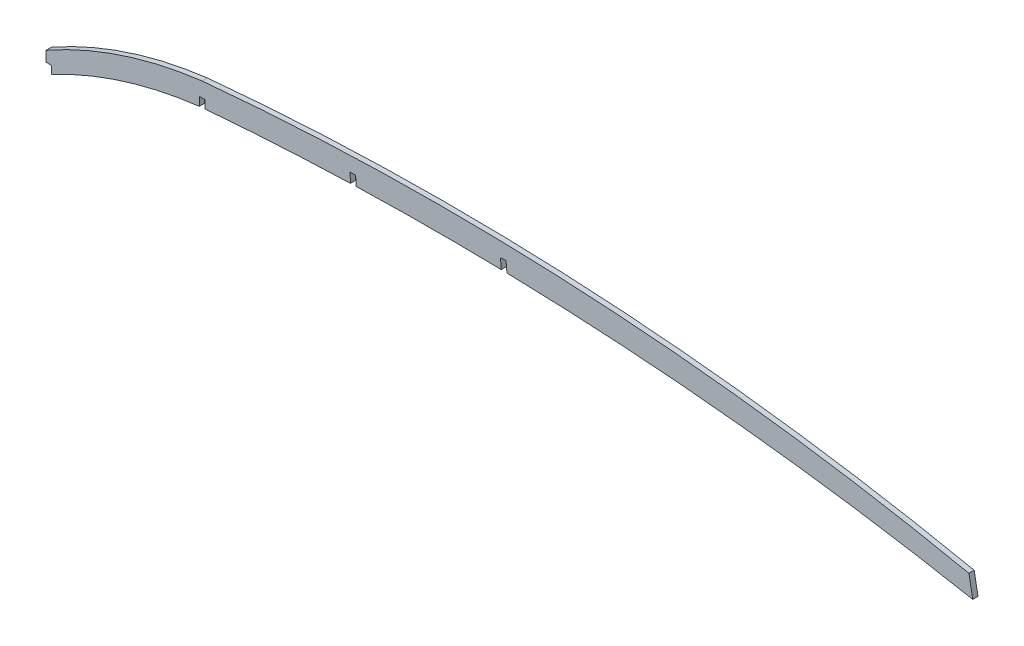
SolidWorks part; units mm, degrees
material "Balsa"
ref_plane "Front Plane" through (0, 0, 0) normal (0, 0, 1) x (1, 0, 0)
ref_plane "Top Plane" through (0, 0, 0) normal (0, 1, 0) x (1, 0, 0)
ref_plane "Right Plane" through (0, 0, 0) normal (1, 0, 0) x (0, 0, -1)
sketch "Sketch1" plane through (0, 0, 0) normal (0, 0, 1) x (1, 0, 0)
  line L2 (0, 0) -> (0, 169.3685) construction
  line L4 (93.98, 106.68) -> (556.5761, 106.68) construction
  line L9 (0, 106.68) -> (93.98, 106.68) construction
  line L14 (555.6382, 111.8229) -> (555.6382, 106.68) construction
  line L17 (555.6382, 111.8229) -> (557.917, 99.3265)
  line L19 (0, 106.68) -> (0, 93.98)
  line L20 (93.98, 137.668) -> (93.98, 123.7947) construction
  arc A6 (0, 106.68) -> (93.98, 137.668) centre (125.0054, -114.43) cw
  arc A8 (93.98, 137.668) -> (555.6382, 111.8229) centre (239.5165, -1398.7972) cw
  arc A9 (0, 93.98) -> (93.98, 123.7947) centre (122.3372, -128.6174) cw
  arc A25 (93.98, 123.7947) -> (557.917, 99.3265) centre (236.8486, -1577.8511) cw
  dimension "D4" = 254
  dimension "D2" = 93.98
  dimension "D8" = 1543.3426
  dimension "D9" = 100.334
  dimension "D3" = 30.988
  dimension "D12" = 254
  dimension "D14" = 1707.6328
  dimension "D1" = 106.68
  dimension "D5" = 462.5961
  dimension "D6" = 0.9378
  dimension "D7" = 5.1429
  dimension "D10" = 12.7025
  dimension "D11" = 12.7
  dimension "D13" = 13.8733
extrude "Boss-Extrude1" add sketch "Sketch1" along normal blind 3.175 contours A9 A25 L17 A8 A6 L19 region at (551.2665, 104.5698, 0)
sketch "Sketch2" plane through (0, 0, 3.175) normal (0, 0, 1) x (1, 0, 0)
  line L0 (0, 0) -> (0, 93.98) construction
  line L1 (0, 0) -> (93.98, 0) construction
  line L2 (93.98, 0) -> (93.98, 128.7725) construction
  line L3 (93.98, 0) -> (190.373, 0) construction
  line L4 (0, 93.98) -> (3.3528, 93.98)
  line L5 (0, 93.98) -> (0, 100.457)
  line L6 (0, 100.457) -> (3.3528, 100.457)
  line L7 (3.3528, 93.98) -> (3.3528, 100.457)
  line L8 (92.2909, 128.8487) -> (95.6691, 128.8487)
  line L9 (92.2909, 128.8487) -> (92.2909, 116.1487)
  line L10 (92.2909, 116.1487) -> (95.6691, 116.1487)
  line L11 (95.6691, 128.8487) -> (95.6691, 116.1487)
  line L12 (190.373, 0) -> (184.7454, 134.6815) construction
  line L15 (183.0546, 134.6871) -> (186.4298, 134.8282)
  line L16 (183.0546, 134.6871) -> (183.5848, 121.9982)
  line L17 (186.4298, 134.8282) -> (186.96, 122.1393)
  line L18 (183.5848, 121.9982) -> (186.96, 122.1393)
  line L21 (184.7454, 134.6815) -> (182.7802, 134.5994) construction
  line L22 (295.918, -122.9242) -> (299.0813, -122.6519)
  line L23 (276.8619, 135.4735) -> (273.6986, 135.2013)
  line L24 (298.5332, -116.2845) -> (295.3699, -116.5568)
  line L25 (274.2467, 128.8339) -> (277.41, 129.1062)
  line L26 (273.6986, 135.2013) -> (274.2467, 128.8339)
  line L27 (295.3699, -116.5568) -> (295.918, -122.9242)
  line L28 (276.8619, 135.4735) -> (277.41, 129.1062)
  line L29 (298.5332, -116.2845) -> (299.0813, -122.6519)
  line L30 (298.5332, -116.2845) -> (299.0813, -122.6519)
  line L32 (295.3699, -116.5568) -> (295.918, -122.9242)
  line L35 (298.5332, -116.2845) -> (295.3699, -116.5568)
  line L37 (295.918, -122.9242) -> (299.0813, -122.6519)
  line L38 (190.373, 0) -> (508.8709, 0) construction
  line L39 (275.2802, 135.3374) -> (286.9301, 0) construction
  line L41 (273.5908, 135.2685) -> (276.9566, 135.5582)
  line L42 (273.5908, 135.2685) -> (274.68, 122.6152)
  line L43 (276.9566, 135.5582) -> (278.0458, 122.905)
  line L44 (274.68, 122.6152) -> (278.0458, 122.905)
  point P20 (184.7422, 134.7577)
  point P31 (275.2737, 135.4133)
  point P36 (93.98, 128.8487)
  dimension "D1" = 93.98
  dimension "D2" = 6.477
  dimension "D3" = 3.3528
  dimension "D4" = 93.98
  dimension "D5" = 128.7725
  dimension "D6" = 3.3782
  dimension "D7" = 12.7
  dimension "D8" = 96.393
  dimension "D9" = 87.607
  dimension "D10" = 134.7991
  dimension "D11" = 0.0762
  dimension "D12" = 3.3782
  dimension "D13" = 85.08
  dimension "D14" = 96.5571
  dimension "D15" = 135.8379
  dimension "D16" = 0.0762
  dimension "D17" = 3.3782
  dimension "D18" = 12.7
  dimension "D19" = 12.7
  dimension "D20" = 0.0762
extrude "Cut-Extrude1" cut sketch "Sketch2" against normal through all
equation "\"slotwidth\"=0.167708"
